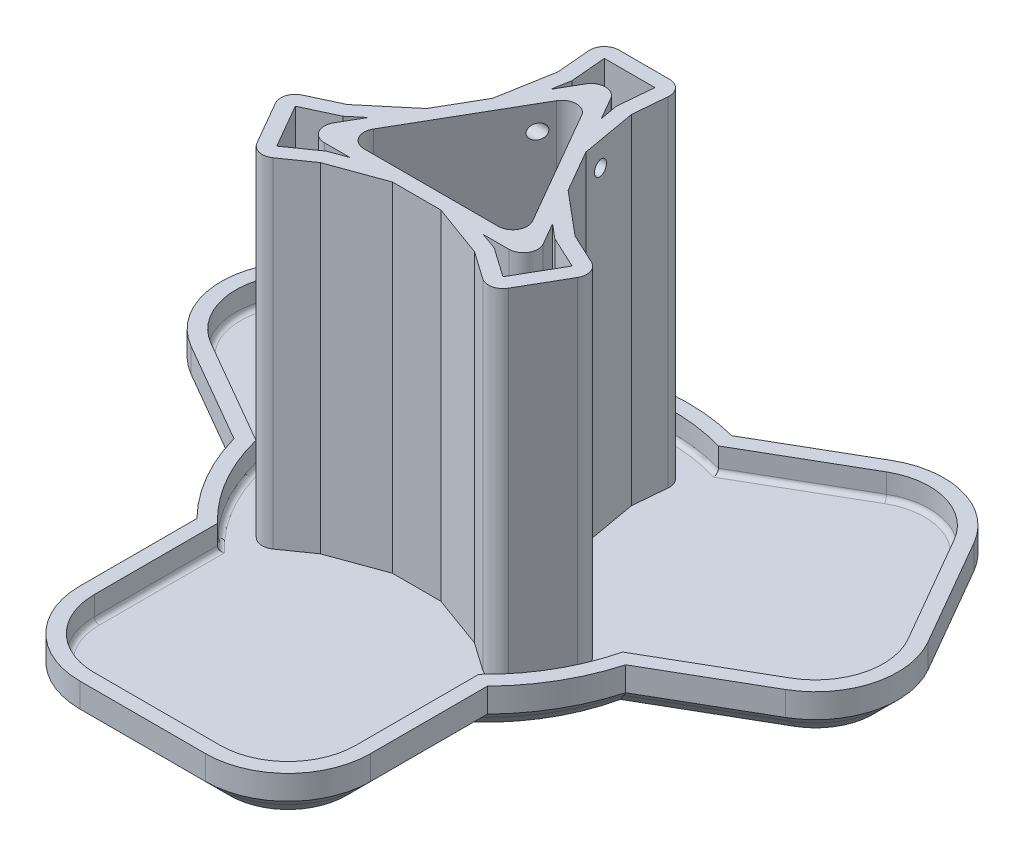
SolidWorks part; units mm, degrees
note: '?' marks a value the reader was unsure of.
ref_plane "前视基准面" through (0, 0, 0) normal (0, 0, 1) x (1, 0, 0)
ref_plane "上视基准面" through (0, 0, 0) normal (0, 1, 0) x (1, 0, 0)
ref_plane "右视基准面" through (0, 0, 0) normal (1, 0, 0) x (0, 0, -1)
other "Configuration Table"
sketch "草图1" plane through (0, 0, 0) normal (0, 1, 0) x (1, 0, 0)
  line L0 (0, 0) -> (0, 132.3895) construction
  line L1 (0, 0) -> (0, -137.3851) construction
  line L2 (0, 0) -> (215.1509, 0) construction
  line L3 (0, 0) -> (134.3926, 77.5916) construction
  line L4 (0, 0) -> (-134.3926, 77.5916) construction
  line L5 (0, -40) -> (55.6916, -40) construction
  line L6 (-28, -28.5657) -> (-28, -68.5657)
  line L7 (-10.7386, 38.5316) -> (-45.3796, 58.5316)
  line L8 (28, -68.5657) -> (-28, -68.5657)
  line L9 (-73.3796, 10.0341) -> (-45.3796, 58.5316)
  line L10 (28, -28.5657) -> (28, -68.5657)
  line L11 (-38.7386, -9.9659) -> (-73.3796, 10.0341)
  line L12 (38.7386, -9.9659) -> (73.3796, 10.0341)
  line L13 (45.3796, 58.5316) -> (73.3796, 10.0341)
  line L14 (10.7386, 38.5316) -> (45.3796, 58.5316)
  circle A0 centre (0, 0) radius 40
  circle A1 centre (0, -40) radius 25 construction
  circle A2 centre (-34.641, 20) radius 25 construction
  circle A3 centre (34.641, 20) radius 25 construction
  point P16 (0, 0)
  point P23 (0, -68.5657)
  point P32 (0, 0)
  dimension "D2" = 80
  dimension "D3" = 50
  dimension "D5" = 28
  dimension "D1" = 120
  dimension "D6" = 40
  dimension "D4" = 3
  dimension "D7" = 3
extrude "凸台-拉伸1" add sketch "草图1" along normal blind 5 contours A0 | A0 L7 L9 L11 | A0 L12 L13 L14 | A0 L6 L8 L10
sketch "草图3" plane through (0, 5, 0) normal (0, 1, 0) x (1, 0, 0)
  line L0 (0, 28) -> (24.2487, -14)
  line L1 (0, 0) -> (134.3926, 77.5916) construction
  line L2 (0, 0) -> (0, 132.3895) construction
  line L3 (0, 0) -> (0, -137.3851) construction
  line L4 (0, 0) -> (-134.3926, 77.5916) construction
  line L5 (0, 0) -> (0, -137.3851) construction
  line L6 (0, 0) -> (-134.3926, 77.5916) construction
  line L7 (0, 0) -> (134.3926, 77.5916) construction
  line L8 (24.2487, -14) -> (-24.2487, -14)
  line L9 (-24.2487, -14) -> (0, 28)
  line L10 (0, 22) -> (19.0526, -11)
  line L11 (19.0526, -11) -> (-19.0526, -11)
  line L12 (-19.0526, -11) -> (0, 22)
  line L13 (5, -14) -> (15.9238, -17.9759)
  line L14 (15.9238, -17.9759) -> (24.3288, -23.8612)
  line L15 (0, 0) -> (24.2487, -14) construction
  line L17 (23.5295, -4.8024) -> (32.8288, -9.1388)
  line L18 (24.3288, -23.8612) -> (32.8288, -9.1388)
  line L19 (14.6244, 2.6699) -> (23.5295, -4.8024)
  line L20 (-5, -14) -> (-15.9238, -17.9759)
  line L21 (-15.9238, -17.9759) -> (-24.3288, -23.8612)
  line L22 (-32.8288, -9.1388) -> (-24.3288, -23.8612)
  line L23 (-23.5295, -4.8024) -> (-32.8288, -9.1388)
  line L24 (-14.6244, 2.6699) -> (-23.5295, -4.8024)
  line L25 (-9.6244, 11.3301) -> (-7.6057, 22.7784)
  line L26 (-7.6057, 22.7784) -> (-8.5, 33)
  line L27 (8.5, 33) -> (-8.5, 33)
  line L28 (7.6057, 22.7784) -> (8.5, 33)
  line L29 (9.6244, 11.3301) -> (7.6057, 22.7784)
  line L30 (-14.6244, 2.6699) -> (-23.5295, -4.8024)
  line L31 (-23.5295, -4.8024) -> (-32.8288, -9.1388)
  line L32 (-32.8288, -9.1388) -> (-24.3288, -23.8612)
  line L33 (-15.9238, -17.9759) -> (-24.3288, -23.8612)
  line L34 (-5, -14) -> (-15.9238, -17.9759)
  line L35 (5, -14) -> (15.9238, -17.9759)
  line L36 (15.9238, -17.9759) -> (24.3288, -23.8612)
  line L37 (24.3288, -23.8612) -> (32.8288, -9.1388)
  line L38 (23.5295, -4.8024) -> (32.8288, -9.1388)
  line L39 (14.6244, 2.6699) -> (23.5295, -4.8024)
  line L40 (5.529, -11) -> (17.321, -15.2919)
  line L41 (17.321, -15.2919) -> (23.3677, -19.5259)
  line L42 (23.3677, -19.5259) -> (28.5938, -10.4741)
  line L43 (21.9037, -7.3544) -> (28.5938, -10.4741)
  line L44 (12.2908, 0.7118) -> (21.9037, -7.3544)
  line L45 (-12.2908, 0.7118) -> (-21.9037, -7.3544)
  line L46 (-21.9037, -7.3544) -> (-28.5938, -10.4741)
  line L47 (-28.5938, -10.4741) -> (-23.3677, -19.5259)
  line L48 (-17.321, -15.2919) -> (-23.3677, -19.5259)
  line L49 (-5.529, -11) -> (-17.321, -15.2919)
  line L50 (6.7618, 10.2882) -> (4.5827, 22.6464)
  line L51 (4.5827, 22.6464) -> (5.2261, 30)
  line L52 (5.2261, 30) -> (-5.2261, 30)
  line L53 (-4.5827, 22.6464) -> (-5.2261, 30)
  line L54 (-6.7618, 10.2882) -> (-4.5827, 22.6464)
  line L55 (-12.696, 0.3717) -> (-21.9037, -7.3544) construction
  line L56 (-6.0261, -11.1809) -> (-17.321, -15.2919) construction
  line L57 (6.0261, -11.1809) -> (17.321, -15.2919) construction
  line L58 (12.696, 0.3717) -> (21.9037, -7.3544) construction
  line L59 (-6.6699, 10.8092) -> (-4.5827, 22.6464) construction
  line L60 (6.6699, 10.8092) -> (4.5827, 22.6464) construction
  point P13 (12.1244, 7)
  point P17 (0, 0)
  point P20 (28.5788, -16.5)
  point P38 (0, 0)
  dimension "D1" = 3
  dimension "D2" = 14
  dimension "D5" = 5
  dimension "D6" = 20
  dimension "D7" = 195
  dimension "D8" = 8.5
  dimension "D9" = 5
  dimension "D3" = 3
  dimension "D11" = 0
  dimension "D12" = 3
  dimension "D10" = 3
extrude "凸台-拉伸2" add sketch "草图3" along normal blind 70 contours L11 L49 L8 L40 | L0 L44 L43 L42 L41 L40 L8 L13 L14 L18 L17 L19 | L8 L49 L48 L47 L46 L45 L9 L24 L23 L22 L21 L20 | L12 L54 L9 L45 | L9 L54 L53 L52 L51 L50 L0 L29 L28 L27 L26 L25 | L50 L10 L44 L0 | L44 L10 L11 L40 L8 L0 | L49 L11 L12 L45 L9 L8 | L54 L12 L10 L50 L0 L9
fillet "圆角1" radius 15 6 edges at (28, 2.5, 68.5657) (-28, 2.5, 68.5657) (-73.3796, 2.5, -10.0341) (-45.3796, 2.5, -58.5316) (73.3796, 2.5, -10.0341) (45.3796, 2.5, -58.5316)
fillet "圆角2" radius 3 6 edges at (0, 40, -28) (0, 40, -22) (24.2487, 40, 14) (19.0526, 40, 11) (-19.0526, 40, 11) (-24.2487, 40, 14)
sketch "草图6" plane through (0, 0, 0) normal (0, -1, 0) x (1, 0, 0)
  line L0 (0, 0) -> (0, 137.3851) construction
  line L1 (0, 0) -> (215.1509, 0) construction
  line L2 (0, 0) -> (0, -132.3895) construction
  line L3 (0, 0) -> (0, -132.3895) construction
  line L4 (0, 0) -> (215.1509, 0) construction
  circle A1 centre (0, 0) radius 3.5
  circle A2 centre (0, 7) radius 1.5
  circle A3 centre (7, 0) radius 1.5
  circle A4 centre (-7, 0) radius 1.5
  circle A5 centre (0, -7) radius 1.5
  dimension "D1" = 7
  dimension "D2" = 3
  dimension "D3" = 3
  dimension "D4" = 7
  dimension "D5" = 7
extrude "切除-拉伸1" cut sketch "草图6" against normal blind 5
fillet "圆角3" radius 3 6 edges at (-8.5, 40, -33) (8.5, 40, -33) (32.8288, 40, 9.1388) (-32.8288, 40, 9.1388) (-24.3288, 40, 23.8612) (24.3288, 40, 23.8612)
sketch "草图7" plane through (0, 0, 0) normal (1, 0, 0) x (0, 0, -1)
  line L0 (0, 0) -> (80.2302, 0) construction
  line L1 (0, 0) -> (132.3895, 0) construction
  line L2 (0, 0) -> (0, 66.7325) construction
  line L3 (15, 0) -> (15, 66.7325) construction
  line L5 (11.3301, 75) -> (22.7784, 75) construction
  circle A0 centre (15, 70) radius 1.5
  dimension "D2" = 3
  dimension "D3" = 5
  dimension "D1" = 15
extrude "切除-拉伸2" cut sketch "草图7" against normal blind 10 and the other way blind 10
ref_plane "基准面1" through (7, 0, 0) normal (1, 0, 0) x (0, 0, -1)
ref_axis "基准轴1" through (0, 57.75, 0) along (0, -1, 0)?
chamfer "倒角1" distance 2 angle 45 6 edges at (9.5263, 5, -5.5) (-9.5263, 5, -5.5) (0, 5, 11) (-16.4545, 5, 9.5) (16.4545, 5, 9.5) (0, 5, -19)
sketch "草图8" plane through (0, 5, 0) normal (0, 1, 0) x (1, 0, 0)
  line L0 (-30, -29.3939) -> (-30, -53.5657)
  line L1 (-13, -70.5657) -> (13, -70.5657)
  line L2 (30, -53.5657) -> (30, -29.3939)
  line L3 (40.4558, -11.2838) -> (61.3893, 0.8021)
  line L4 (67.6117, 24.0245) -> (54.6117, 46.5412)
  line L5 (31.3893, 52.7636) -> (10.4558, 40.6777)
  line L6 (-10.4558, 40.6777) -> (-31.3893, 52.7636)
  line L7 (-54.6117, 46.5412) -> (-67.6117, 24.0245)
  line L8 (-61.3893, 0.8021) -> (-40.4558, -11.2838)
  line L9 (-13, -68.5657) -> (13, -68.5657)
  line L10 (28, -53.5657) -> (28, -28.5657)
  line L11 (38.7386, -9.9659) -> (60.3893, 2.5341)
  line L12 (65.8796, 23.0245) -> (52.8796, 45.5412)
  line L13 (32.3893, 51.0316) -> (10.7386, 38.5316)
  line L14 (-10.7386, 38.5316) -> (-32.3893, 51.0316)
  line L15 (-52.8796, 45.5412) -> (-65.8796, 23.0245)
  line L16 (-60.3893, 2.5341) -> (-38.7386, -9.9659)
  line L17 (-28, -28.5657) -> (-28, -53.5657)
  line L18 (-13, -68.5657) -> (13, -68.5657)
  line L19 (28, -53.5657) -> (28, -28.5657)
  line L20 (38.7386, -9.9659) -> (60.3893, 2.5341)
  line L21 (65.8796, 23.0245) -> (52.8796, 45.5412)
  line L22 (32.3893, 51.0316) -> (10.7386, 38.5316)
  line L23 (-10.7386, 38.5316) -> (-32.3893, 51.0316)
  line L24 (-52.8796, 45.5412) -> (-65.8796, 23.0245)
  line L25 (-60.3893, 2.5341) -> (-38.7386, -9.9659)
  line L26 (-28, -28.5657) -> (-28, -53.5657)
  line L27 (-27, -28.1425) -> (-27, -53.5657)
  line L28 (-13, -67.5657) -> (13, -67.5657)
  line L29 (27, -53.5657) -> (27, -28.1425)
  line L30 (37.8721, -9.3114) -> (59.8893, 3.4002)
  line L31 (65.0136, 22.5245) -> (52.0136, 45.0412)
  line L32 (32.8893, 50.1655) -> (10.8721, 37.4539)
  line L33 (-10.8721, 37.4539) -> (-32.8893, 50.1655)
  line L34 (-52.0136, 45.0412) -> (-65.0136, 22.5245)
  line L35 (-59.8893, 3.4002) -> (-37.8721, -9.3114)
  arc A0 (-40.4558, -11.2838) -> (-30, -29.3939) centre (0, 0) ccw
  arc A1 (-30, -53.5657) -> (-13, -70.5657) centre (-13, -53.5657) ccw
  arc A2 (13, -70.5657) -> (30, -53.5657) centre (13, -53.5657) ccw
  arc A3 (30, -29.3939) -> (40.4558, -11.2838) centre (0, 0) ccw
  arc A4 (61.3893, 0.8021) -> (67.6117, 24.0245) centre (52.8893, 15.5245) ccw
  arc A5 (54.6117, 46.5412) -> (31.3893, 52.7636) centre (39.8893, 38.0412) ccw
  arc A6 (10.4558, 40.6777) -> (-10.4558, 40.6777) centre (0, 0) ccw
  arc A7 (-31.3893, 52.7636) -> (-54.6117, 46.5412) centre (-39.8893, 38.0412) ccw
  arc A8 (-67.6117, 24.0245) -> (-61.3893, 0.8021) centre (-52.8893, 15.5245) ccw
  arc A9 (13, -68.5657) -> (28, -53.5657) centre (13, -53.5657) ccw
  arc A10 (28, -28.5657) -> (38.7386, -9.9659) centre (0, 0) ccw
  arc A11 (60.3893, 2.5341) -> (65.8796, 23.0245) centre (52.8893, 15.5245) ccw
  arc A12 (52.8796, 45.5412) -> (32.3893, 51.0316) centre (39.8893, 38.0412) ccw
  arc A13 (10.7386, 38.5316) -> (-10.7386, 38.5316) centre (0, 0) ccw
  arc A14 (-32.3893, 51.0316) -> (-52.8796, 45.5412) centre (-39.8893, 38.0412) ccw
  arc A15 (-65.8796, 23.0245) -> (-60.3893, 2.5341) centre (-52.8893, 15.5245) ccw
  arc A16 (-38.7386, -9.9659) -> (-28, -28.5657) centre (0, 0) ccw
  arc A17 (-28, -53.5657) -> (-13, -68.5657) centre (-13, -53.5657) ccw
  arc A18 (13, -68.5657) -> (28, -53.5657) centre (13, -53.5657) ccw
  arc A19 (28, -28.5657) -> (38.7386, -9.9659) centre (0, 0) ccw
  arc A20 (60.3893, 2.5341) -> (65.8796, 23.0245) centre (52.8893, 15.5245) ccw
  arc A21 (52.8796, 45.5412) -> (32.3893, 51.0316) centre (39.8893, 38.0412) ccw
  arc A22 (10.7386, 38.5316) -> (-10.7386, 38.5316) centre (0, 0) ccw
  arc A23 (-32.3893, 51.0316) -> (-52.8796, 45.5412) centre (-39.8893, 38.0412) ccw
  arc A24 (-65.8796, 23.0245) -> (-60.3893, 2.5341) centre (-52.8893, 15.5245) ccw
  arc A25 (-38.7386, -9.9659) -> (-28, -28.5657) centre (0, 0) ccw
  arc A26 (-28, -53.5657) -> (-13, -68.5657) centre (-13, -53.5657) ccw
  arc A27 (-27, -53.5657) -> (-13, -67.5657) centre (-13, -53.5657) ccw
  arc A28 (13, -67.5657) -> (27, -53.5657) centre (13, -53.5657) ccw
  arc A29 (27, -28.1425) -> (37.8721, -9.3114) centre (0, 0) ccw
  arc A30 (59.8893, 3.4002) -> (65.0136, 22.5245) centre (52.8893, 15.5245) ccw
  arc A31 (52.0136, 45.0412) -> (32.8893, 50.1655) centre (39.8893, 38.0412) ccw
  arc A32 (10.8721, 37.4539) -> (-10.8721, 37.4539) centre (0, 0) ccw
  arc A33 (-32.8893, 50.1655) -> (-52.0136, 45.0412) centre (-39.8893, 38.0412) ccw
  arc A34 (-65.0136, 22.5245) -> (-59.8893, 3.4002) centre (-52.8893, 15.5245) ccw
  arc A35 (-37.8721, -9.3114) -> (-27, -28.1425) centre (0, 0) ccw
  line M79 (-13, -68.5657) -> (13, -68.5657)
  arc M80 (13, -68.5657) -> (28, -53.5657) centre (13, -53.5657) ccw
  line M81 (28, -53.5657) -> (28, -28.5657)
  arc M82 (28, -28.5657) -> (38.7386, -9.9659) centre (0, 0) ccw
  line M83 (38.7386, -9.9659) -> (60.3893, 2.5341)
  arc M84 (60.3893, 2.5341) -> (65.8796, 23.0245) centre (52.8893, 15.5245) ccw
  line M85 (65.8796, 23.0245) -> (52.8796, 45.5412)
  arc M86 (52.8796, 45.5412) -> (32.3893, 51.0316) centre (39.8893, 38.0412) ccw
  line M87 (32.3893, 51.0316) -> (10.7386, 38.5316)
  arc M88 (10.7386, 38.5316) -> (-10.7386, 38.5316) centre (0, 0) ccw
  line M89 (-10.7386, 38.5316) -> (-32.3893, 51.0316)
  arc M90 (-32.3893, 51.0316) -> (-52.8796, 45.5412) centre (-39.8893, 38.0412) ccw
  line M91 (-52.8796, 45.5412) -> (-65.8796, 23.0245)
  arc M92 (-65.8796, 23.0245) -> (-60.3893, 2.5341) centre (-52.8893, 15.5245) ccw
  line M93 (-60.3893, 2.5341) -> (-38.7386, -9.9659)
  arc M94 (-38.7386, -9.9659) -> (-28, -28.5657) centre (0, 0) ccw
  line M95 (-28, -28.5657) -> (-28, -53.5657)
  arc M96 (-28, -53.5657) -> (-13, -68.5657) centre (-13, -53.5657) ccw
  dimension "D1" = 0
  dimension "D2" = 2
  dimension "D3" = 1
extrude "凸台-拉伸3" add sketch "草图8" along normal blind 5 contours L7 A8 L8 A0 L0 A1 L1 A2 L2 A3 L3 A4 L4 A5 L5 A6 L6 A7 M79 M96 M95 M94 M93 M92 M91 M90 M89 M88 M87 M86 M85 M84 M83 M82 M81 M80 | A35 L35 A34 L34 A33 L33 A32 L32 A31 L31 A30 L30 A29 L29 A28 L28 A27 L27 M96 M79 M80 M81 M82 M83 M84 M85 M86 M87 M88 M89 M90 M91 M92 M93 M94 M95
chamfer "倒角2" distance 2 angle 45 18 edges at (0, 5, -40) (21.564, 5, -44.7816) (43.7716, 5, -52.5301) (59.3796, 5, -34.2829) (67.3782, 5, -11.6422) (34.641, 5, 20) (49.564, 5, 3.7159) (-21.564, 5, -44.7816) (28, 5, 41.0657) (-43.7716, 5, -52.5301) (23.6066, 5, 64.1723) (-59.3796, 5, -34.2829) (0, 5, 68.5657) (-67.3782, 5, -11.6422) (-23.6066, 5, 64.1723) (-49.564, 5, 3.7159) (-28, 5, 41.0657) (-34.641, 5, 20)
chamfer "倒角3" distance 3 angle 45 18 edges at (-34.641, 0, 20) (-28, 0, 41.0657) (-23.6066, 0, 64.1723) (0, 0, 68.5657) (23.6066, 0, 64.1723) (34.641, 0, 20) (28, 0, 41.0657) (49.564, 0, 3.7159) (67.3782, 0, -11.6422) (59.3796, 0, -34.2829) (43.7716, 0, -52.5301) (21.564, 0, -44.7816) (0, 0, -40) (-49.564, 0, 3.7159) (-21.564, 0, -44.7816) (-67.3782, 0, -11.6422) (-43.7716, 0, -52.5301) (-59.3796, 0, -34.2829)
fillet "圆角4" radius 1 18 edges at (-33.775, 5, 19.5) (-27, 5, 40.8541) (-22.8995, 5, 63.4652) (0, 5, 67.5657) (22.8995, 5, 63.4652) (27, 5, 40.8541) (33.775, 5, 19.5) (48.8807, 5, 2.9556) (66.4122, 5, -11.9011) (58.5136, 5, -33.7829) (43.5127, 5, -51.5641) (21.8807, 5, -43.8097) (0, 5, -39) (-21.8807, 5, -43.8097) (-43.5127, 5, -51.5641) (-58.5136, 5, -33.7829) (-66.4122, 5, -11.9011) (-48.8807, 5, 2.9556)
